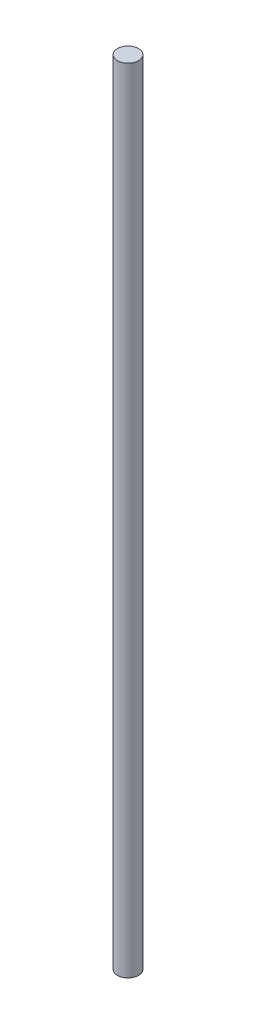
SolidWorks part; units mm, degrees
ref_plane "Front Plane" through (0, 0, 0) normal (0, 0, 1) x (1, 0, 0)
ref_plane "Top Plane" through (0, 0, 0) normal (0, 1, 0) x (1, 0, 0)
ref_plane "Right Plane" through (0, 0, 0) normal (1, 0, 0) x (0, 0, -1)
sketch "Sketch1" plane through (0, 0, 0) normal (0, 1, 0) x (1, 0, 0)
  circle A0 centre (0, 0) radius 4
extrude "Boss-Extrude1" add sketch "Sketch1" along normal blind 300
ref_axis "Axis1" through (0, 300, 0) along (0, -1, 0)
